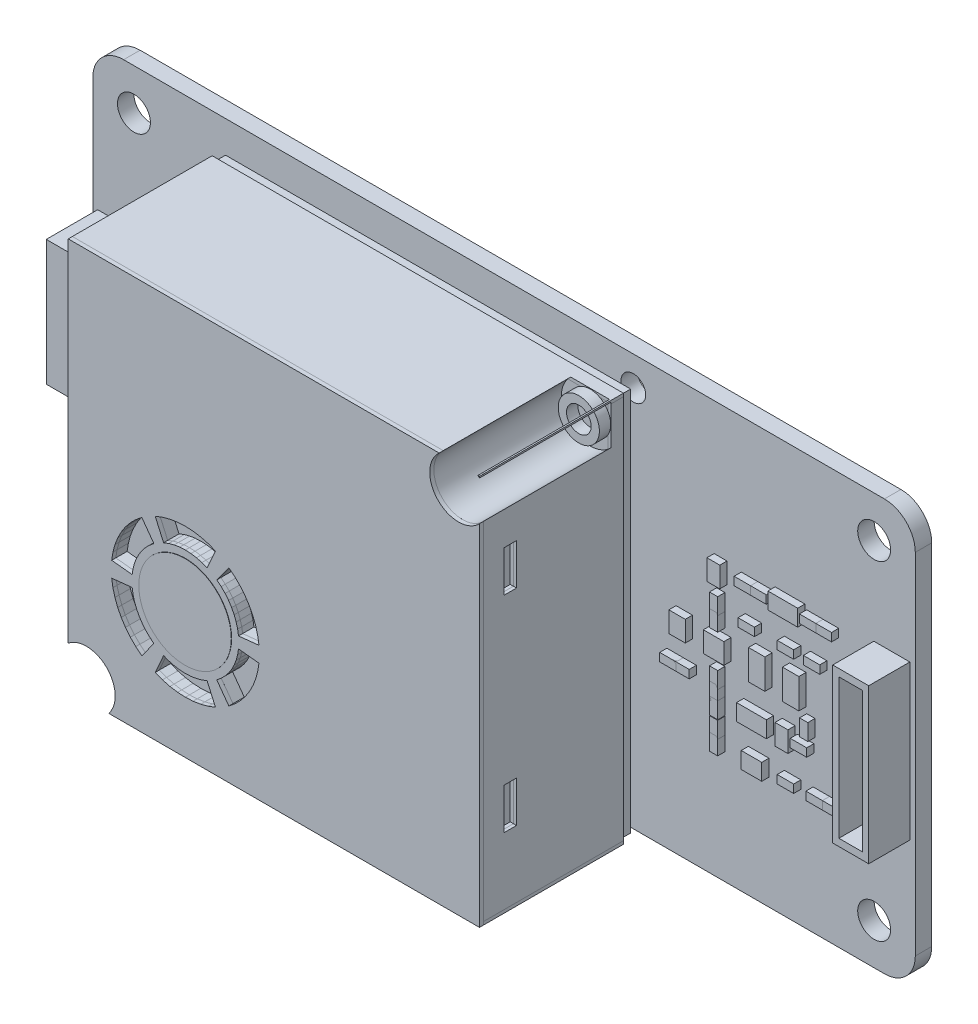
SolidWorks part; units mm, degrees
other "Corps_HM3301"
other "PCB_Seeed_v1_0"
ref_plane "Plan de face" through (0, 0, 0) normal (0, 0, 1) x (1, 0, 0)
ref_plane "Plan de dessus" through (0, 0, 0) normal (0, 1, 0) x (1, 0, 0)
ref_plane "Plan de droite" through (0, 0, 0) normal (1, 0, 0) x (0, 0, -1)
sketch "Esquisse1" plane through (0, 0, 0) normal (0, 0, 1) x (1, 0, 0)
  line L0 (-37, -20) -> (37, -20)
  line L1 (40, -17) -> (40, 17)
  line L2 (37, 20) -> (-37, 20)
  line L3 (-40, 17) -> (-40, -17)
  arc A0 (37, -20) -> (40, -17) centre (37, -17) ccw
  arc A1 (40, 17) -> (37, 20) centre (37, 17) ccw
  arc A2 (-37, 20) -> (-40, 17) centre (-37, 17) ccw
  arc A3 (-40, -17) -> (-37, -20) centre (-37, -17) ccw
  circle A4 centre (-36, -16) radius 1.6
  circle A5 centre (-36, 16) radius 1.6
  circle A6 centre (36, -16) radius 1.6
  circle A7 centre (36, 16) radius 1.6
  circle A8 centre (-23.622, -17.018) radius 1.2
  circle A9 centre (12.573, 17.145) radius 1.2
extrude "PCB_Eagle_80x40_R3_ep_ESTIMEE_1_6" add sketch "Esquisse1" along normal blind 1.6 separate body
sketch "Esquisse2" plane through (0, 0, 0) normal (0, 0, 1) x (1, 0, 0)
  line L1 (-25.089, -18.487) -> (14.311, -18.487)
  line L2 (-25.089, -18.487) -> (-25.089, 18.913)
  line L3 (-25.089, 18.913) -> (14.311, 18.913)
  line L4 (14.311, -18.487) -> (14.311, 18.913)
extrude "HM3301_corps_40x38x15_Z_estime" add sketch "Esquisse2" along normal blind 14.6 from offset 3.6 separate body
sketch "Esquisse3" plane through (0, 0, 0) normal (0, 0, 1) x (1, 0, 0)
  line L1 (-25.389, -18.787) -> (14.611, -18.787)
  line L2 (-25.389, -18.787) -> (-25.389, 19.213)
  line L3 (-25.389, 19.213) -> (14.611, 19.213)
  line L4 (14.611, -18.787) -> (14.611, 19.213)
extrude "Capot_superieur_ep_simplifiee" add sketch "Esquisse3" along normal blind 0.4 from offset 18.2 separate body
sketch "Esquisse4" plane through (0, 0, 0) normal (0, 0, 1) x (1, 0, 0)
  line L1 (-25.389, -18.787) -> (14.611, -18.787)
  line L2 (-25.389, -18.787) -> (-25.389, -18.487)
  line L3 (-25.389, -18.487) -> (14.611, -18.487)
  line L4 (14.611, -18.787) -> (14.611, -18.487)
  line L6 (-25.389, 18.913) -> (14.611, 18.913)
  line L7 (-25.389, 18.913) -> (-25.389, 19.213)
  line L8 (-25.389, 19.213) -> (14.611, 19.213)
  line L9 (14.611, 18.913) -> (14.611, 19.213)
extrude "Flancs_capot_simplifies" add sketch "Esquisse4" along normal blind 13.6 from offset 4.6 separate body
sketch "Esquisse5" plane through (0, 0, 0) normal (0, 0, 1) x (1, 0, 0)
  line L1 (-25.389, -18.487) -> (-25.089, -18.487)
  line L2 (-25.389, -18.487) -> (-25.389, 18.913)
  line L3 (-25.389, 18.913) -> (-25.089, 18.913)
  line L4 (-25.089, -18.487) -> (-25.089, 18.913)
  line L6 (14.311, -18.487) -> (14.611, -18.487)
  line L7 (14.311, -18.487) -> (14.311, 18.913)
  line L8 (14.311, 18.913) -> (14.611, 18.913)
  line L9 (14.611, -18.487) -> (14.611, 18.913)
extrude "Faces_capot_simplifiees" add sketch "Esquisse5" along normal blind 13.6 from offset 4.6 separate body
sketch "Esquisse6" plane through (0, 0, 0) normal (0, 0, 1) x (1, 0, 0)
  circle A0 centre (-23.622, -17.018) radius 2.8
  circle A1 centre (12.573, 17.145) radius 2.8
extrude "Degagements_vis_ESTIMES" cut sketch "Esquisse6" against normal blind 12.8 from offset 18.6
sketch "Esquisse7" plane through (0, 0, 0) normal (0, 0, 1) x (1, 0, 0)
  line L0 (-6.8394, -5.7474) -> (-6.9573, -5.003)
  line L1 (-6.9573, -5.003) -> (-7.1524, -4.2751)
  line L2 (-7.1524, -4.2751) -> (-7.4225, -3.5715)
  line L3 (-7.4225, -3.5715) -> (-7.7646, -2.9)
  line L4 (-7.7646, -2.9) -> (-8.1751, -2.2679)
  line L5 (-8.1751, -2.2679) -> (-8.6494, -1.6823)
  line L6 (-8.6494, -1.6823) -> (-9.1823, -1.1494)
  line L7 (-9.1823, -1.1494) -> (-9.7679, -0.6751)
  line L8 (-9.7679, -0.6751) -> (-10.9435, -2.2931)
  line L9 (-10.9435, -2.2931) -> (-10.5205, -2.6356)
  line L10 (-10.5205, -2.6356) -> (-10.1356, -3.0205)
  line L11 (-10.1356, -3.0205) -> (-9.7931, -3.4435)
  line L12 (-9.7931, -3.4435) -> (-9.4967, -3.9)
  line L13 (-9.4967, -3.9) -> (-9.2496, -4.385)
  line L14 (-9.2496, -4.385) -> (-9.0545, -4.8931)
  line L15 (-9.0545, -4.8931) -> (-8.9136, -5.4189)
  line L16 (-8.9136, -5.4189) -> (-8.8285, -5.9565)
  line L17 (-8.8285, -5.9565) -> (-6.8394, -5.7474)
  line L18 (-11.0715, 0.0775) -> (-11.7751, 0.3476)
  line L19 (-11.7751, 0.3476) -> (-12.503, 0.5427)
  line L20 (-12.503, 0.5427) -> (-13.2474, 0.6606)
  line L21 (-13.2474, 0.6606) -> (-14, 0.7)
  line L22 (-14, 0.7) -> (-14.7526, 0.6606)
  line L23 (-14.7526, 0.6606) -> (-15.497, 0.5427)
  line L24 (-15.497, 0.5427) -> (-16.2249, 0.3476)
  line L25 (-16.2249, 0.3476) -> (-16.9285, 0.0775)
  line L26 (-16.9285, 0.0775) -> (-16.115, -1.7496)
  line L27 (-16.115, -1.7496) -> (-15.6069, -1.5545)
  line L28 (-15.6069, -1.5545) -> (-15.0811, -1.4136)
  line L29 (-15.0811, -1.4136) -> (-14.5435, -1.3285)
  line L30 (-14.5435, -1.3285) -> (-14, -1.3)
  line L31 (-14, -1.3) -> (-13.4565, -1.3285)
  line L32 (-13.4565, -1.3285) -> (-12.9189, -1.4136)
  line L33 (-12.9189, -1.4136) -> (-12.3931, -1.5545)
  line L34 (-12.3931, -1.5545) -> (-11.885, -1.7496)
  line L35 (-11.885, -1.7496) -> (-11.0715, 0.0775)
  line L36 (-18.2321, -0.6751) -> (-18.8177, -1.1494)
  line L37 (-18.8177, -1.1494) -> (-19.3506, -1.6823)
  line L38 (-19.3506, -1.6823) -> (-19.8249, -2.2679)
  line L39 (-19.8249, -2.2679) -> (-20.2354, -2.9)
  line L40 (-20.2354, -2.9) -> (-20.5775, -3.5715)
  line L41 (-20.5775, -3.5715) -> (-20.8476, -4.2751)
  line L42 (-20.8476, -4.2751) -> (-21.0427, -5.003)
  line L43 (-21.0427, -5.003) -> (-21.1606, -5.7474)
  line L44 (-21.1606, -5.7474) -> (-19.1715, -5.9565)
  line L45 (-19.1715, -5.9565) -> (-19.0864, -5.4189)
  line L46 (-19.0864, -5.4189) -> (-18.9455, -4.8931)
  line L47 (-18.9455, -4.8931) -> (-18.7504, -4.385)
  line L48 (-18.7504, -4.385) -> (-18.5033, -3.9)
  line L49 (-18.5033, -3.9) -> (-18.2069, -3.4435)
  line L50 (-18.2069, -3.4435) -> (-17.8644, -3.0205)
  line L51 (-17.8644, -3.0205) -> (-17.4795, -2.6356)
  line L52 (-17.4795, -2.6356) -> (-17.0565, -2.2931)
  line L53 (-17.0565, -2.2931) -> (-18.2321, -0.6751)
  line L54 (-21.1606, -7.2526) -> (-21.0427, -7.997)
  line L55 (-21.0427, -7.997) -> (-20.8476, -8.7249)
  line L56 (-20.8476, -8.7249) -> (-20.5775, -9.4285)
  line L57 (-20.5775, -9.4285) -> (-20.2354, -10.1)
  line L58 (-20.2354, -10.1) -> (-19.8249, -10.7321)
  line L59 (-19.8249, -10.7321) -> (-19.3506, -11.3177)
  line L60 (-19.3506, -11.3177) -> (-18.8177, -11.8506)
  line L61 (-18.8177, -11.8506) -> (-18.2321, -12.3249)
  line L62 (-18.2321, -12.3249) -> (-17.0565, -10.7069)
  line L63 (-17.0565, -10.7069) -> (-17.4795, -10.3644)
  line L64 (-17.4795, -10.3644) -> (-17.8644, -9.9795)
  line L65 (-17.8644, -9.9795) -> (-18.2069, -9.5565)
  line L66 (-18.2069, -9.5565) -> (-18.5033, -9.1)
  line L67 (-18.5033, -9.1) -> (-18.7504, -8.615)
  line L68 (-18.7504, -8.615) -> (-18.9455, -8.1069)
  line L69 (-18.9455, -8.1069) -> (-19.0864, -7.5811)
  line L70 (-19.0864, -7.5811) -> (-19.1715, -7.0435)
  line L71 (-19.1715, -7.0435) -> (-21.1606, -7.2526)
  line L72 (-16.9285, -13.0775) -> (-16.2249, -13.3476)
  line L73 (-16.2249, -13.3476) -> (-15.497, -13.5427)
  line L74 (-15.497, -13.5427) -> (-14.7526, -13.6606)
  line L75 (-14.7526, -13.6606) -> (-14, -13.7)
  line L76 (-14, -13.7) -> (-13.2474, -13.6606)
  line L77 (-13.2474, -13.6606) -> (-12.503, -13.5427)
  line L78 (-12.503, -13.5427) -> (-11.7751, -13.3476)
  line L79 (-11.7751, -13.3476) -> (-11.0715, -13.0775)
  line L80 (-11.0715, -13.0775) -> (-11.885, -11.2504)
  line L81 (-11.885, -11.2504) -> (-12.3931, -11.4455)
  line L82 (-12.3931, -11.4455) -> (-12.9189, -11.5864)
  line L83 (-12.9189, -11.5864) -> (-13.4565, -11.6715)
  line L84 (-13.4565, -11.6715) -> (-14, -11.7)
  line L85 (-14, -11.7) -> (-14.5435, -11.6715)
  line L86 (-14.5435, -11.6715) -> (-15.0811, -11.5864)
  line L87 (-15.0811, -11.5864) -> (-15.6069, -11.4455)
  line L88 (-15.6069, -11.4455) -> (-16.115, -11.2504)
  line L89 (-16.115, -11.2504) -> (-16.9285, -13.0775)
  line L90 (-9.7679, -12.3249) -> (-9.1823, -11.8506)
  line L91 (-9.1823, -11.8506) -> (-8.6494, -11.3177)
  line L92 (-8.6494, -11.3177) -> (-8.1751, -10.7321)
  line L93 (-8.1751, -10.7321) -> (-7.7646, -10.1)
  line L94 (-7.7646, -10.1) -> (-7.4225, -9.4285)
  line L95 (-7.4225, -9.4285) -> (-7.1524, -8.7249)
  line L96 (-7.1524, -8.7249) -> (-6.9573, -7.997)
  line L97 (-6.9573, -7.997) -> (-6.8394, -7.2526)
  line L98 (-6.8394, -7.2526) -> (-8.8285, -7.0435)
  line L99 (-8.8285, -7.0435) -> (-8.9136, -7.5811)
  line L100 (-8.9136, -7.5811) -> (-9.0545, -8.1069)
  line L101 (-9.0545, -8.1069) -> (-9.2496, -8.615)
  line L102 (-9.2496, -8.615) -> (-9.4967, -9.1)
  line L103 (-9.4967, -9.1) -> (-9.7931, -9.5565)
  line L104 (-9.7931, -9.5565) -> (-10.1356, -9.9795)
  line L105 (-10.1356, -9.9795) -> (-10.5205, -10.3644)
  line L106 (-10.5205, -10.3644) -> (-10.9435, -10.7069)
  line L107 (-10.9435, -10.7069) -> (-9.7679, -12.3249)
extrude "Grille_ventilateur_ESTIMEE" cut sketch "Esquisse7" against normal blind 1.5 from offset 18.6
sketch "Esquisse8" plane through (0, 0, 0) normal (0, 0, 1) x (1, 0, 0)
  circle A0 centre (-14, -6.5) radius 4.5
extrude "Etiquette_ventilateur_simplifiee" add sketch "Esquisse8" along normal blind 0.03 from offset 18.6 separate body
sketch "Esquisse9" plane through (0, 0, 0) normal (0, 0, 1) x (1, 0, 0)
  line L1 (-20, -19) -> (-16.5, -19)
  line L2 (-20, -19) -> (-20, -18.2)
  line L3 (-20, -18.2) -> (-16.5, -18.2)
  line L4 (-16.5, -19) -> (-16.5, -18.2)
  line L6 (6, -19) -> (9.5, -19)
  line L7 (6, -19) -> (6, -18.2)
  line L8 (6, -18.2) -> (9.5, -18.2)
  line L9 (9.5, -19) -> (9.5, -18.2)
  line L11 (14, -12) -> (14.8, -12)
  line L12 (14, -12) -> (14, -8)
  line L13 (14, -8) -> (14.8, -8)
  line L14 (14.8, -12) -> (14.8, -8)
  line L16 (14, 8) -> (14.8, 8)
  line L17 (14, 8) -> (14, 12)
  line L18 (14, 12) -> (14.8, 12)
  line L19 (14.8, 8) -> (14.8, 12)
extrude "Fentes_laterales_ESTIMEES" cut sketch "Esquisse9" against normal blind 1.2 from offset 16.2
sketch "Esquisse10" plane through (0, 0, 0) normal (0, 0, 1) x (1, 0, 0)
  line L1 (-20, -19) -> (-16.5, -19)
  line L2 (-20, -19) -> (-20, -18.2)
  line L3 (-20, -18.2) -> (-16.5, -18.2)
  line L4 (-16.5, -19) -> (-16.5, -18.2)
  line L6 (6, -19) -> (9.5, -19)
  line L7 (6, -19) -> (6, -18.2)
  line L8 (6, -18.2) -> (9.5, -18.2)
  line L9 (9.5, -19) -> (9.5, -18.2)
extrude "Fentes_basses_ESTIMEES" cut sketch "Esquisse10" against normal blind 1.2 from offset 8.2
sketch "Esquisse11" plane through (0, 0, 0) normal (0, 0, 1) x (1, 0, 0)
  line L1 (-39.5276, -6.1) -> (-31.8276, -6.1)
  line L2 (-39.5276, -6.1) -> (-39.5276, 6.1)
  line L3 (-39.5276, 6.1) -> (-31.8276, 6.1)
  line L4 (-31.8276, -6.1) -> (-31.8276, 6.1)
extrude "Grove_position_Eagle_hauteur_ESTIMEE" add sketch "Esquisse11" along normal blind 5 from offset 1.6 separate body
sketch "Esquisse12" plane through (0, 0, 0) normal (0, 0, 1) x (1, 0, 0)
  line L1 (-40, -5.3) -> (-33.5, -5.3)
  line L2 (-40, -5.3) -> (-40, 5.3)
  line L3 (-40, 5.3) -> (-33.5, 5.3)
  line L4 (-33.5, -5.3) -> (-33.5, 5.3)
extrude "Ouverture_Grove" cut sketch "Esquisse12" against normal blind 3.5 from offset 5.9
sketch "Esquisse13" plane through (0, 0, 0) normal (0, 0, 1) x (1, 0, 0)
  line L1 (-38.5, -3.25) -> (-33, -3.25)
  line L2 (-38.5, -3.25) -> (-38.5, -2.75)
  line L3 (-38.5, -2.75) -> (-33, -2.75)
  line L4 (-33, -3.25) -> (-33, -2.75)
  line L6 (-38.5, -1.25) -> (-33, -1.25)
  line L7 (-38.5, -1.25) -> (-38.5, -0.75)
  line L8 (-38.5, -0.75) -> (-33, -0.75)
  line L9 (-33, -1.25) -> (-33, -0.75)
  line L11 (-38.5, 0.75) -> (-33, 0.75)
  line L12 (-38.5, 0.75) -> (-38.5, 1.25)
  line L13 (-38.5, 1.25) -> (-33, 1.25)
  line L14 (-33, 0.75) -> (-33, 1.25)
  line L16 (-38.5, 2.75) -> (-33, 2.75)
  line L17 (-38.5, 2.75) -> (-38.5, 3.25)
  line L18 (-38.5, 3.25) -> (-33, 3.25)
  line L19 (-33, 2.75) -> (-33, 3.25)
extrude "Broches_Grove" add sketch "Esquisse13" along normal blind 0.5 from offset 3 separate body
sketch "Esquisse14" plane through (0, 0, 0) normal (0, 0, 1) x (1, 0, 0)
  line L1 (35.969, -7.5) -> (39.469, -7.5)
  line L2 (35.969, -7.5) -> (35.969, 7.5)
  line L3 (35.969, 7.5) -> (39.469, 7.5)
  line L4 (39.469, -7.5) -> (39.469, 7.5)
extrude "Connecteur_8P_position_Eagle_H_ESTIMEE" add sketch "Esquisse14" along normal blind 4 from offset 1.6 separate body
sketch "Esquisse15" plane through (0, 0, 0) normal (0, 0, 1) x (1, 0, 0)
  line L1 (36.569, -6.8) -> (38.869, -6.8)
  line L2 (36.569, -6.8) -> (36.569, 6.8)
  line L3 (36.569, 6.8) -> (38.869, 6.8)
  line L4 (38.869, -6.8) -> (38.869, 6.8)
extrude "Cavite_8P_simplifiee" cut sketch "Esquisse15" against normal blind 2.7 from offset 5.6
sketch "Esquisse16" plane through (0, 0, 0) normal (0, 0, 1) x (1, 0, 0)
  circle A0 centre (-23.622, -17.018) radius 2
  circle A1 centre (-23.622, -17.018) radius 1.2
  circle A2 centre (12.573, 17.145) radius 2
  circle A3 centre (12.573, 17.145) radius 1.2
extrude "Tetes_vis_simplifiees" add sketch "Esquisse16" along normal blind 1.1 from offset 5.8 separate body
sketch "Esquisse17" plane through (0, 0, 0) normal (0, 0, 1) x (1, 0, 0)
  line L1 (20.682, -3.467) -> (21.482, -3.467)
  line L2 (20.682, -3.467) -> (20.682, -1.867)
  line L3 (20.682, -1.867) -> (21.482, -1.867)
  line L4 (21.482, -3.467) -> (21.482, -1.867)
extrude "Composant_Eagle_1" add sketch "Esquisse17" along normal blind 0.7 from offset 1.6 separate body
sketch "Esquisse18" plane through (0, 0, 0) normal (0, 0, 1) x (1, 0, 0)
  line L1 (20.082, -1.127) -> (22.082, -1.127)
  line L2 (20.082, -1.127) -> (20.082, 0.873)
  line L3 (20.082, 0.873) -> (22.082, 0.873)
  line L4 (22.082, -1.127) -> (22.082, 0.873)
extrude "Composant_Eagle_2" add sketch "Esquisse18" along normal blind 0.7 from offset 1.6 separate body
sketch "Esquisse19" plane through (0, 0, 0) normal (0, 0, 1) x (1, 0, 0)
  line L1 (16.726, -1.127) -> (18.326, -1.127)
  line L2 (16.726, -1.127) -> (16.726, 0.873)
  line L3 (16.726, 0.873) -> (18.326, 0.873)
  line L4 (18.326, -1.127) -> (18.326, 0.873)
extrude "Composant_Eagle_3" add sketch "Esquisse19" along normal blind 0.7 from offset 1.6 separate body
sketch "Esquisse20" plane through (0, 0, 0) normal (0, 0, 1) x (1, 0, 0)
  line L1 (17.107, -3.956) -> (18.707, -3.956)
  line L2 (17.107, -3.956) -> (17.107, -3.156)
  line L3 (17.107, -3.156) -> (18.707, -3.156)
  line L4 (18.707, -3.956) -> (18.707, -3.156)
extrude "Composant_Eagle_4" add sketch "Esquisse20" along normal blind 0.7 from offset 1.6 separate body
sketch "Esquisse21" plane through (0, 0, 0) normal (0, 0, 1) x (1, 0, 0)
  line L1 (15.837, -3.956) -> (17.437, -3.956)
  line L2 (15.837, -3.956) -> (15.837, -3.156)
  line L3 (15.837, -3.156) -> (17.437, -3.156)
  line L4 (17.437, -3.956) -> (17.437, -3.156)
extrude "Composant_Eagle_5" add sketch "Esquisse21" along normal blind 0.7 from offset 1.6 separate body
sketch "Esquisse22" plane through (0, 0, 0) normal (0, 0, 1) x (1, 0, 0)
  line L1 (20.682, 1.359) -> (21.482, 1.359)
  line L2 (20.682, 1.359) -> (20.682, 2.959)
  line L3 (20.682, 2.959) -> (21.482, 2.959)
  line L4 (21.482, 1.359) -> (21.482, 2.959)
extrude "Composant_Eagle_6" add sketch "Esquisse22" along normal blind 0.7 from offset 1.6 separate body
sketch "Esquisse23" plane through (0, 0, 0) normal (0, 0, 1) x (1, 0, 0)
  line L1 (20.682, -4.737) -> (21.482, -4.737)
  line L2 (20.682, -4.737) -> (20.682, -3.137)
  line L3 (20.682, -3.137) -> (21.482, -3.137)
  line L4 (21.482, -4.737) -> (21.482, -3.137)
extrude "Composant_Eagle_7" add sketch "Esquisse23" along normal blind 0.7 from offset 1.6 separate body
sketch "Esquisse24" plane through (0, 0, 0) normal (0, 0, 1) x (1, 0, 0)
  line L1 (20.682, 2.756) -> (21.482, 2.756)
  line L2 (20.682, 2.756) -> (20.682, 4.356)
  line L3 (20.682, 4.356) -> (21.482, 4.356)
  line L4 (21.482, 2.756) -> (21.482, 4.356)
extrude "Composant_Eagle_8" add sketch "Esquisse24" along normal blind 0.7 from offset 1.6 separate body
sketch "Esquisse25" plane through (0, 0, 0) normal (0, 0, 1) x (1, 0, 0)
  line L1 (23.315, -5.245) -> (26.215, -5.245)
  line L2 (23.315, -5.245) -> (23.315, -3.645)
  line L3 (23.315, -3.645) -> (26.215, -3.645)
  line L4 (26.215, -5.245) -> (26.215, -3.645)
extrude "Composant_Eagle_9" add sketch "Esquisse25" along normal blind 0.7 from offset 1.6 separate body
sketch "Esquisse26" plane through (0, 0, 0) normal (0, 0, 1) x (1, 0, 0)
  line L1 (23.765, -9.055) -> (25.765, -9.055)
  line L2 (23.765, -9.055) -> (23.765, -7.455)
  line L3 (23.765, -7.455) -> (25.765, -7.455)
  line L4 (25.765, -9.055) -> (25.765, -7.455)
extrude "Composant_Eagle_10" add sketch "Esquisse26" along normal blind 0.7 from offset 1.6 separate body
sketch "Esquisse27" plane through (0, 0, 0) normal (0, 0, 1) x (1, 0, 0)
  line L1 (20.682, -6.007) -> (21.482, -6.007)
  line L2 (20.682, -6.007) -> (20.682, -4.407)
  line L3 (20.682, -4.407) -> (21.482, -4.407)
  line L4 (21.482, -6.007) -> (21.482, -4.407)
extrude "Composant_Eagle_11" add sketch "Esquisse27" along normal blind 0.7 from offset 1.6 separate body
sketch "Esquisse28" plane through (0, 0, 0) normal (0, 0, 1) x (1, 0, 0)
  line L1 (20.682, -9.055) -> (21.482, -9.055)
  line L2 (20.682, -9.055) -> (20.682, -7.455)
  line L3 (20.682, -7.455) -> (21.482, -7.455)
  line L4 (21.482, -9.055) -> (21.482, -7.455)
extrude "Composant_Eagle_12" add sketch "Esquisse28" along normal blind 0.7 from offset 1.6 separate body
sketch "Esquisse29" plane through (0, 0, 0) normal (0, 0, 1) x (1, 0, 0)
  line L1 (20.682, -7.658) -> (21.482, -7.658)
  line L2 (20.682, -7.658) -> (20.682, -6.058)
  line L3 (20.682, -6.058) -> (21.482, -6.058)
  line L4 (21.482, -7.658) -> (21.482, -6.058)
extrude "Composant_Eagle_13" add sketch "Esquisse29" along normal blind 0.7 from offset 1.6 separate body
sketch "Esquisse30" plane through (0, 0, 0) normal (0, 0, 1) x (1, 0, 0)
  line L1 (31.585, -8.528) -> (33.185, -8.528)
  line L2 (31.585, -8.528) -> (31.585, -7.728)
  line L3 (31.585, -7.728) -> (33.185, -7.728)
  line L4 (33.185, -8.528) -> (33.185, -7.728)
extrude "Composant_Eagle_14" add sketch "Esquisse30" along normal blind 0.7 from offset 1.6 separate body
sketch "Esquisse31" plane through (0, 0, 0) normal (0, 0, 1) x (1, 0, 0)
  line L1 (30.061, -8.528) -> (31.661, -8.528)
  line L2 (30.061, -8.528) -> (30.061, -7.728)
  line L3 (30.061, -7.728) -> (31.661, -7.728)
  line L4 (31.661, -8.528) -> (31.661, -7.728)
extrude "Composant_Eagle_15" add sketch "Esquisse31" along normal blind 0.7 from offset 1.6 separate body
sketch "Esquisse32" plane through (0, 0, 0) normal (0, 0, 1) x (1, 0, 0)
  line L1 (27.061, -5.445) -> (28.311, -5.445)
  line L2 (27.061, -5.445) -> (27.061, -3.445)
  line L3 (27.061, -3.445) -> (28.311, -3.445)
  line L4 (28.311, -5.445) -> (28.311, -3.445)
extrude "Composant_Eagle_16" add sketch "Esquisse32" along normal blind 0.7 from offset 1.6 separate body
sketch "Esquisse33" plane through (0, 0, 0) normal (0, 0, 1) x (1, 0, 0)
  line L1 (28.537, -4.845) -> (30.137, -4.845)
  line L2 (28.537, -4.845) -> (28.537, -4.045)
  line L3 (28.537, -4.045) -> (30.137, -4.045)
  line L4 (30.137, -4.845) -> (30.137, -4.045)
extrude "Composant_Eagle_17" add sketch "Esquisse33" along normal blind 0.7 from offset 1.6 separate body
sketch "Esquisse34" plane through (0, 0, 0) normal (0, 0, 1) x (1, 0, 0)
  line L1 (29.445, -3.467) -> (30.245, -3.467)
  line L2 (29.445, -3.467) -> (29.445, -1.867)
  line L3 (29.445, -1.867) -> (30.245, -1.867)
  line L4 (30.245, -3.467) -> (30.245, -1.867)
extrude "Composant_Eagle_18" add sketch "Esquisse34" along normal blind 0.7 from offset 1.6 separate body
sketch "Esquisse35" plane through (0, 0, 0) normal (0, 0, 1) x (1, 0, 0)
  line L1 (27.267, -8.528) -> (28.867, -8.528)
  line L2 (27.267, -8.528) -> (27.267, -7.728)
  line L3 (27.267, -7.728) -> (28.867, -7.728)
  line L4 (28.867, -8.528) -> (28.867, -7.728)
extrude "Composant_Eagle_19" add sketch "Esquisse35" along normal blind 0.7 from offset 1.6 separate body
sketch "Esquisse36" plane through (0, 0, 0) normal (0, 0, 1) x (1, 0, 0)
  line L1 (20.433, 5.115) -> (21.683, 5.115)
  line L2 (20.433, 5.115) -> (20.433, 7.115)
  line L3 (20.433, 7.115) -> (21.683, 7.115)
  line L4 (21.683, 5.115) -> (21.683, 7.115)
extrude "Composant_Eagle_20" add sketch "Esquisse36" along normal blind 0.7 from offset 1.6 separate body
sketch "Esquisse37" plane through (0, 0, 0) normal (0, 0, 1) x (1, 0, 0)
  line L1 (26.363, 5.677) -> (29.263, 5.677)
  line L2 (26.363, 5.677) -> (26.363, 7.277)
  line L3 (26.363, 7.277) -> (29.263, 7.277)
  line L4 (29.263, 5.677) -> (29.263, 7.277)
extrude "Composant_Eagle_21" add sketch "Esquisse37" along normal blind 0.7 from offset 1.6 separate body
sketch "Esquisse38" plane through (0, 0, 0) normal (0, 0, 1) x (1, 0, 0)
  line L1 (24.6, 6.077) -> (26.2, 6.077)
  line L2 (24.6, 6.077) -> (24.6, 6.877)
  line L3 (24.6, 6.877) -> (26.2, 6.877)
  line L4 (26.2, 6.077) -> (26.2, 6.877)
extrude "Composant_Eagle_22" add sketch "Esquisse38" along normal blind 0.7 from offset 1.6 separate body
sketch "Esquisse39" plane through (0, 0, 0) normal (0, 0, 1) x (1, 0, 0)
  line L1 (23.076, 6.077) -> (24.676, 6.077)
  line L2 (23.076, 6.077) -> (23.076, 6.877)
  line L3 (23.076, 6.877) -> (24.676, 6.877)
  line L4 (24.676, 6.077) -> (24.676, 6.877)
extrude "Composant_Eagle_23" add sketch "Esquisse39" along normal blind 0.7 from offset 1.6 separate body
sketch "Esquisse40" plane through (0, 0, 0) normal (0, 0, 1) x (1, 0, 0)
  line L1 (30.95, 6.077) -> (32.55, 6.077)
  line L2 (30.95, 6.077) -> (30.95, 6.877)
  line L3 (30.95, 6.877) -> (32.55, 6.877)
  line L4 (32.55, 6.077) -> (32.55, 6.877)
extrude "Composant_Eagle_24" add sketch "Esquisse40" along normal blind 0.7 from offset 1.6 separate body
sketch "Esquisse41" plane through (0, 0, 0) normal (0, 0, 1) x (1, 0, 0)
  line L1 (29.426, 6.077) -> (31.026, 6.077)
  line L2 (29.426, 6.077) -> (29.426, 6.877)
  line L3 (29.426, 6.877) -> (31.026, 6.877)
  line L4 (31.026, 6.077) -> (31.026, 6.877)
extrude "Composant_Eagle_25" add sketch "Esquisse41" along normal blind 0.7 from offset 1.6 separate body
sketch "Esquisse42" plane through (0, 0, 0) normal (0, 0, 1) x (1, 0, 0)
  line L1 (27.775, -1.323) -> (29.375, -1.323)
  line L2 (27.775, -1.323) -> (27.775, 1.577)
  line L3 (27.775, 1.577) -> (29.375, 1.577)
  line L4 (29.375, -1.323) -> (29.375, 1.577)
extrude "Composant_Eagle_26" add sketch "Esquisse42" along normal blind 0.7 from offset 1.6 separate body
sketch "Esquisse43" plane through (0, 0, 0) normal (0, 0, 1) x (1, 0, 0)
  line L1 (24.473, -1.323) -> (26.073, -1.323)
  line L2 (24.473, -1.323) -> (24.473, 1.577)
  line L3 (24.473, 1.577) -> (26.073, 1.577)
  line L4 (26.073, -1.323) -> (26.073, 1.577)
extrude "Composant_Eagle_27" add sketch "Esquisse43" along normal blind 0.7 from offset 1.6 separate body
sketch "Esquisse44" plane through (0, 0, 0) normal (0, 0, 1) x (1, 0, 0)
  line L1 (27.267, 2.775) -> (28.867, 2.775)
  line L2 (27.267, 2.775) -> (27.267, 3.575)
  line L3 (27.267, 3.575) -> (28.867, 3.575)
  line L4 (28.867, 2.775) -> (28.867, 3.575)
extrude "Composant_Eagle_28" add sketch "Esquisse44" along normal blind 0.7 from offset 1.6 separate body
sketch "Esquisse45" plane through (0, 0, 0) normal (0, 0, 1) x (1, 0, 0)
  line L1 (23.457, 2.775) -> (25.057, 2.775)
  line L2 (23.457, 2.775) -> (23.457, 3.575)
  line L3 (23.457, 3.575) -> (25.057, 3.575)
  line L4 (25.057, 2.775) -> (25.057, 3.575)
extrude "Composant_Eagle_29" add sketch "Esquisse45" along normal blind 0.7 from offset 1.6 separate body
sketch "Esquisse46" plane through (0, 0, 0) normal (0, 0, 1) x (1, 0, 0)
  line L1 (29.807, 2.775) -> (31.407, 2.775)
  line L2 (29.807, 2.775) -> (29.807, 3.575)
  line L3 (29.807, 3.575) -> (31.407, 3.575)
  line L4 (31.407, 2.775) -> (31.407, 3.575)
extrude "Composant_Eagle_30" add sketch "Esquisse46" along normal blind 0.7 from offset 1.6 separate body
